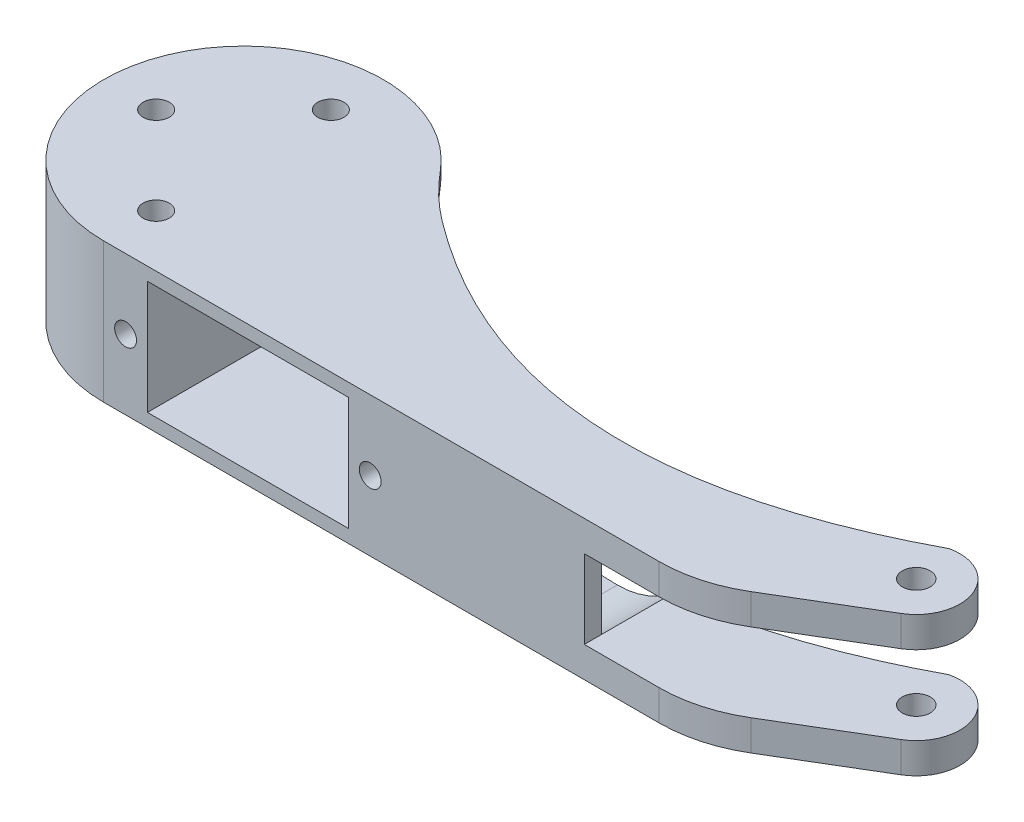
SolidWorks part; units mm, degrees
ref_plane "前视基准面" through (0, 0, 0) normal (0, 0, 1) x (1, 0, 0)
ref_plane "上视基准面" through (0, 0, 0) normal (0, 1, 0) x (1, 0, 0)
ref_plane "右视基准面" through (0, 0, 0) normal (1, 0, 0) x (0, 0, -1)
other "Configuration Table"
sketch "Sketch1" plane through (0, 0, 0) normal (0, 1, 0) x (1, 0, 0)
  line L0 (80, -3.5578) -> (80, -3)
  line L1 (0, -16) -> (80, -16)
  line L2 (80, -16) -> (80, -3)
  line L3 (45, -6) -> (45, -16)
  line L4 (45, -6) -> (7.5685, 14.0968)
  line L5 (45, -6) -> (78.8683, 1.8702)
  line L6 (68, -16) -> (82.5658, -7.2915)
  circle A0 centre (0, 0) radius 16
  circle A1 centre (80, -3) radius 1.6
  circle A2 centre (80, -3) radius 5
  spline S0 degree 2 poles (7.5685, 14.0968) (39.626, -19.032) (78.8683, 1.8702) knots 0 0 0 1 1 1
  point P9 (45, -6)
  point P12 (68, -16)
  dimension "D1" = 32
  dimension "D3" = 3.2
  dimension "D5" = 10
  dimension "D2" = 80
  dimension "D4" = 3
  dimension "D6" = 35
  dimension "D7" = 12
extrude "Boss-Extrude2" add sketch "Sketch1" along normal blind 16 contours S0 A0 | A0 S0 | S0 A0 L1 L3 | S0 L3 L1 L6 L2 A2 | S0 A2 A1 | A2 L2 L6 region at (26.506, 0, 8.6395) region at (-0.0488, 0, 0.0517) region at (61.6179, 0, 9.7761) region at (10.7343, 0, -11.3591) region at (80.6607, 0, 8.1799) region at (83.0218, 0, -0.8045)
fillet "Fillet1" radius 16 1 edges at (68, 8, 16)
sketch "Sketch2" plane through (0, 0, 16) normal (0, 0, 1) x (1, 0, 0)
  line L0 (85, 0) -> (55, 0) construction
  line L1 (0, 0) -> (63.5817, 0) construction
  line L2 (55, 0) -> (55, 16) construction
  line L3 (0, 16) -> (63.5817, 16) construction
  line L4 (85, 0) -> (85, 16) construction
  line L5 (55, 0) -> (55, 4) construction
  line L6 (55, 4) -> (55, 12) construction
  line L8 (55, 12) -> (85, 12)
  line L9 (55, 12) -> (55, 4)
  line L10 (55, 4) -> (85, 4)
  line L11 (85, 12) -> (85, 4)
  dimension "D1" = 30
  dimension "D2" = 4
  dimension "D3" = 8
extrude "Cut-Extrude2" cut sketch "Sketch2" against normal through all contours L10 L11 L8 L9
sketch "Sketch3" plane through (0, 0, 16) normal (0, 0, 1) x (1, 0, 0)
  line L0 (0, 16) -> (0, 0) construction
  line L1 (0, 16) -> (28, 16)
  line L2 (0, 16) -> (0, 14.5)
  line L3 (5, 14.5) -> (28, 14.5)
  line L4 (28, 16) -> (28, 14.5)
  line L5 (28, 14.5) -> (5, 14.5)
  line L6 (28, 14.5) -> (28, 1.5)
  line L7 (28, 1.5) -> (5, 1.5)
  line L8 (0, 14.5) -> (0, 1.5)
  line L9 (5, 8) -> (28, 8) construction
  line L10 (28, 1.5) -> (5, 1.5)
  line L11 (28, 1.5) -> (28, 0)
  line L12 (28, 0) -> (0, 0)
  line L13 (0, 1.5) -> (0, 0)
  line L14 (5, 14.5) -> (28, 14.5)
  line L15 (5, 14.5) -> (5, 1.5)
  line L16 (5, 1.5) -> (28, 1.5)
  line L17 (28, 14.5) -> (28, 1.5)
  line L18 (0.3, 8) -> (5, 8) construction
  line L19 (0.3, 14.5) -> (32.7, 14.5)
  line L20 (0.3, 14.5) -> (0.3, 1.5)
  line L21 (0.3, 1.5) -> (32.7, 1.5)
  line L22 (32.7, 14.5) -> (32.7, 1.5)
  circle A0 centre (30.5, 8) radius 1.25
  circle A1 centre (2.5, 8) radius 1.25
  dimension "D8" = 2.5
  dimension "D9" = 2.5
  dimension "D1" = 1.5
  dimension "D2" = 1.5
  dimension "D3" = 5
  dimension "D4" = 23
  dimension "D5" = 32.4
  dimension "D6" = 4.7
  dimension "D7" = 2.2
  dimension "D10" = 2.2
extrude "Cut-Extrude3" cut sketch "Sketch3" against normal through all contours L5 L15 L7 L6 | A1 | A0 region at (16.5, 8, 16)
sketch "Sketch4" plane through (0, 0, 0) normal (0, -1, 0) x (1, 0, 0)
  circle A0 centre (0, 0) radius 10
  circle A1 centre (0, -10) radius 1.5
  circle A2 centre (-10, 0) radius 1.5
  circle A3 centre (0, 10) radius 1.5
  circle A4 centre (10, 0) radius 1.5
  point P14 (0, 0)
  dimension "D1" = 20
  dimension "D2" = 3
  dimension "D3" = 4
extrude "Cut-Extrude4" cut sketch "Sketch4" against normal through all contours A1 | A2 | A3
fillet "Fillet2" radius 30 2 edges at (13.6421, 15.25, -8.3603) (13.6421, 0.75, -8.3603)
ref_plane "Plane1" through (0, 0, -14) normal (0, 0, 1) x (1, 0, 0)
sketch "Sketch5" plane through (0, 0, -14) normal (0, 0, 1) x (1, 0, 0)
  line L0 (28, 1.5) -> (28, 14.5) construction
  line L1 (55, 4) -> (55, 12) construction
  line L2 (53, 14.5) -> (55, 12.5)
  line L3 (28, 1.5) -> (53, 1.5)
  line L4 (28, 1.5) -> (28, 14.5)
  line L5 (28, 14.5) -> (53, 14.5)
  line L6 (55, 3.5) -> (55, 12.5)
  line L7 (53, 1.5) -> (55, 3.5)
  point P6 (55, 14.5)
  point P9 (55, 1.5)
extrude "Cut-Extrude5" cut sketch "Sketch5" along normal blind 28
fillet "Fillet3" radius 10 2 edges at (53, 14.5, 10.0491) (53, 1.5, 10.0491)
sketch "Sketch6" plane through (0, 0, 14) normal (0, 0, -1) x (-1, 0, 0)
  line L5 (-85, 3.5) -> (-55, 3.5)
  line L6 (-85, 3.5) -> (-85, 12.5)
  line L7 (-85, 12.5) -> (-55, 12.5)
  line L8 (-55, 3.5) -> (-55, 12.5)
extrude "Cut-Extrude6" cut sketch "Sketch6" against normal through all and the other way through all
